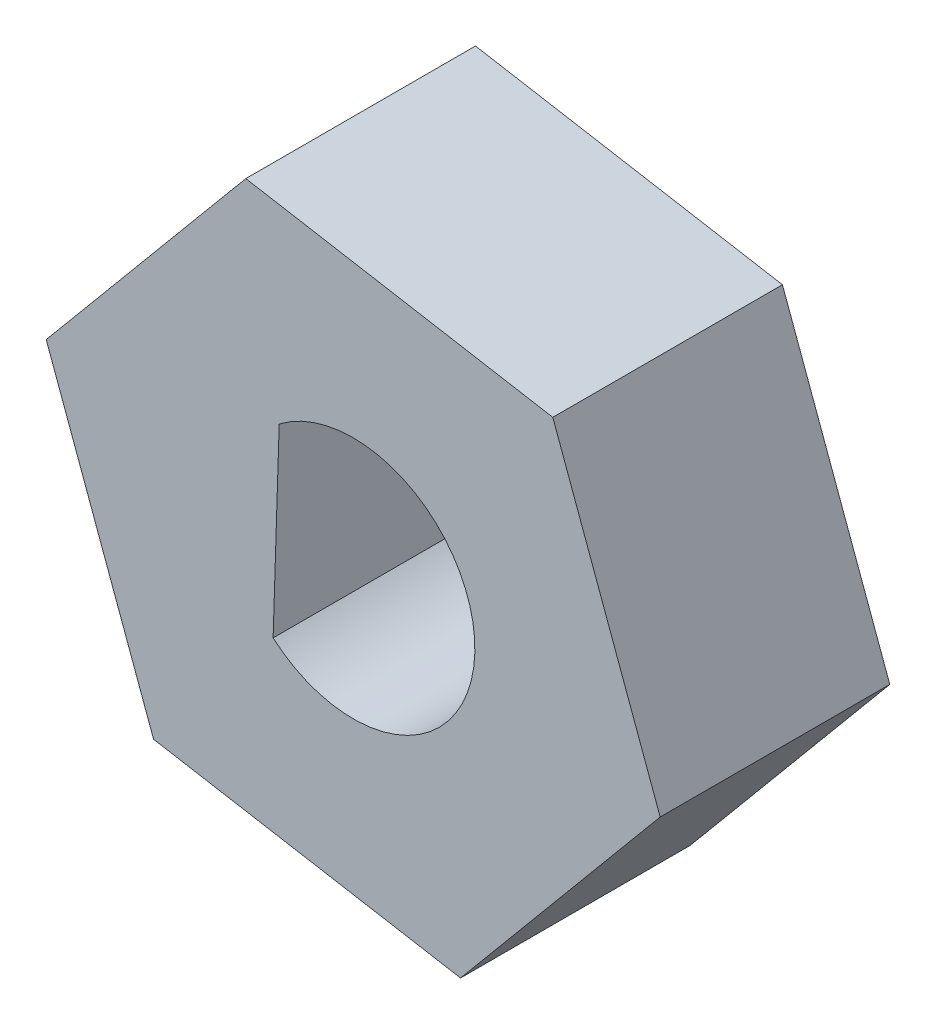
SolidWorks part; units mm, degrees
ref_plane "Front Plane" through (0, 0, 0) normal (0, 0, 1) x (1, 0, 0)
ref_plane "Top Plane" through (0, 0, 0) normal (0, 1, 0) x (1, 0, 0)
ref_plane "Right Plane" through (0, 0, 0) normal (1, 0, 0) x (0, 0, -1)
sketch "Sketch1" plane through (0, 0, 0) normal (0, 0, 1) x (1, 0, 0)
  line L1 (8.6924, 10.4176) -> (-4.6757, 12.7366)
  line L2 (-4.6757, 12.7366) -> (-13.3681, 2.319)
  line L3 (-13.3681, 2.319) -> (-8.6924, -10.4176)
  line L4 (-8.6924, -10.4176) -> (4.6757, -12.7366)
  line L5 (4.6757, -12.7366) -> (13.3681, -2.319)
  line L6 (13.3681, -2.319) -> (8.6924, 10.4176)
  circle A1 centre (0, 0) radius 11.75 construction
  dimension "D4" = 23.5
extrude "Boss-Extrude1" add sketch "Sketch1" along normal blind 10
sketch "Sketch3" plane through (0, 0, 0) normal (0, 0, -1) x (-1, 0, 0)
  line L0 (3.2217, 4.2084) -> (3.4867, -3.9916)
  circle A0 centre (0, 0) radius 5.3
  dimension "D1" = 0
  dimension "D2" = 10.6
  dimension "D3" = 5.3
  dimension "D4" = 5.3
  dimension "D5" = 8.2
extrude "Cut-Extrude1" cut sketch "Sketch3" against normal blind 10 contours L0 A0 region at (0.5962, -0.0193, 0)
